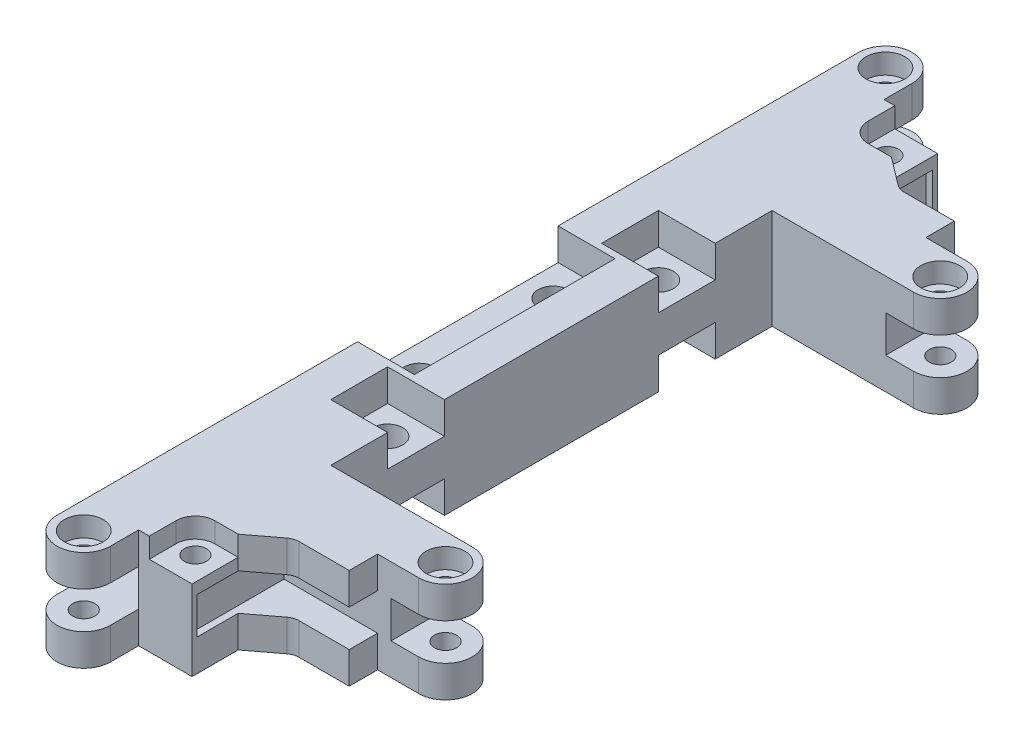
SolidWorks part; units mm, degrees
ref_plane "Front Plane" through (0, 0, 0) normal (0, 0, 1) x (1, 0, 0)
ref_plane "Top Plane" through (0, 0, 0) normal (0, 1, 0) x (1, 0, 0)
ref_plane "Right Plane" through (0, 0, 0) normal (1, 0, 0) x (0, 0, -1)
sketch "Sketch1" plane through (0, 0, 0) normal (0, 1, 0) x (1, 0, 0)
  line L0 (0, 0) -> (0, 41)
  line L1 (0, 41) -> (0, 45.25)
  line L2 (-7.5, 49.75) -> (0, 49.75)
  line L3 (0, 41) -> (6.15, 41)
  line L4 (0, 33) -> (6.15, 33)
  line L5 (0, 45.25) -> (-7.5, 45.25)
  line L6 (0, 49.75) -> (0, 55.75)
  line L7 (0, 55.75) -> (-21, 55.75)
  line L8 (-21, 55.75) -> (-21, 59.95)
  line L9 (-29, 25.8016) -> (-29, 59.95)
  line L10 (-29, 25.8016) -> (-29, 0)
  line L11 (-29, 0) -> (0, 0)
  line L12 (-29, 15) -> (-20.5, 15)
  line L13 (-20.5, 15) -> (-20.5, 0)
  line L14 (0, 33) -> (-15, 33)
  line L15 (-15, 33) -> (-15, 0)
  line L16 (0, 52.75) -> (-13, 52.75)
  line L17 (-13, 52.75) -> (-13, 43)
  line L18 (-13, 43) -> (0, 43)
  line L19 (-13, 52.75) -> (-13, 55.75)
  line L20 (-19.4, 51.75) -> (-19.4, 55.75)
  line L21 (-16.5, 48.85) -> (-13, 48.85)
  line L22 (-15, 16) -> (-23.5, 16)
  line L23 (-23.5, 16) -> (-23.5, 24.5)
  line L24 (-23.5, 24.5) -> (-15, 24.5)
  line L25 (-8.8604, 45.7078) -> (-13, 48.85)
  arc A0 (-7.5, 49.75) -> (-7.5, 45.25) centre (-7.5, 47.5) ccw
  arc A1 (6.15, 41) -> (6.15, 33) centre (6.15, 37) cw
  circle A2 centre (6.15, 37) radius 1.65
  arc A3 (-29, 59.95) -> (-21, 59.95) centre (-25, 59.95) cw
  circle A4 centre (-25, 59.95) radius 1.65
  circle A5 centre (-24.75, 10) radius 2.25
  circle A6 centre (-7.5, 47.5) radius 6.5 construction
  circle A7 centre (-16.5, 51.75) radius 1.65
  circle A8 centre (-25, 59.95) radius 2.9
  circle A9 centre (-16.5, 51.75) radius 2.9
  circle A10 centre (6.15, 37) radius 2.9
  circle A11 centre (-19.25, 20.25) radius 2.25
  point P26 (-24.75, 15)
  point P48 (-23.5, 20.25)
  point P53 (-19.25, 24.5)
  dimension "D1" = 6.15
  dimension "D2" = 3.3
  dimension "D4" = 8
  dimension "D5" = 3.3
  dimension "D15" = 10
  dimension "D16" = 4.5
  dimension "D17" = 13
  dimension "D21" = 3.5
  dimension "D23" = 5.8
  dimension "D24" = 8.5
  dimension "D3" = 8
  dimension "D6" = 6
  dimension "D7" = 4.5
  dimension "D8" = 6.5
  dimension "D9" = 7.5
  dimension "D10" = 4.2
  dimension "D11" = 25
  dimension "D12" = 15
  dimension "8" = 33
  dimension "D13" = 15
  dimension "D14" = 8.5
  dimension "D18" = 3
  dimension "D19" = 2
  dimension "D20" = 13
  dimension "D22" = 4
  dimension "D25" = 1
  dimension "D26" = 8.5
extrude "Boss-Extrude1" add sketch "Sketch1" along normal blind 7.5 and the other way blind 7.5 contours A3 L9 L10 L12 L13 L11 L0 L1 L5 A0 L2 L6 L7 L8 A4 | L13 L12 L10 L11 A5 | A1 L3 L0 L4 A2 | A5 | A8 A4 | A9 A7 | A10 A2 | A9 L17 L19 L7 L20 | L24 L23 L22 L15 A11 | A0 L25 L17 L18 L1 L5 region at (-19.0736, 0, -34.823) region at (0.1292, 0, -37) region at (-24.75, 0, -7.1437) region at (-19.25, 0, -16.1202) region at (-7.6123, 0, -44.6514) region at (-14.75, 0, -48.9441) region at (-18.4926, 0, -49.7574) region at (-24.75, 0, -10) region at (-27.818, 0, -59.95) region at (3.332, 0, -37)
sketch "Sketch2" plane through (0, 0, 0) normal (1, 0, 0) x (0, 0, -1)
  line L0 (55.75, -7.5) -> (55.75, 7.5) construction
  line L1 (55.75, 2.75) -> (63.95, 2.75)
  line L2 (55.75, 2.75) -> (55.75, -2.75)
  line L3 (55.75, -2.75) -> (63.95, -2.75)
  line L4 (63.95, 2.75) -> (63.95, -2.75)
  line L5 (55, 2.75) -> (41, 2.75)
  line L6 (55, 2.75) -> (55, -2.75)
  line L7 (55, -2.75) -> (41, -2.75)
  line L8 (41, 2.75) -> (41, -2.75)
  line L9 (41, -7.5) -> (41, 7.5) construction
  line L10 (63.95, -7.5) -> (63.95, 7.5) construction
  line L11 (55.75, 7.5) -> (48.85, 7.5) construction
  point P12 (63.95, 0)
  dimension "D1" = 14
  dimension "D2" = 5.5
extrude "Cut-Extrude1" cut sketch "Sketch2" against normal through all contours L1 L6 L3 L4 region at (0, 0, -59.85)
extrude "Cut-Extrude7" cut sketch "Sketch2<5>" against normal blind 14 contours L5 L8 L7 L6 region at (0, 0, -48)
sketch "Sketch2<5>" plane through (0, 0, 0) normal (1, 0, 0) x (0, 0, -1) same geometry as "Sketch2"
sketch "Sketch5" plane through (0, 0, 0) normal (1, 0, 0) x (0, 0, -1)
  line L0 (0, 0) -> (41, 0) construction
  line L1 (63.95, 2.75) -> (25.45, 2.75)
  line L2 (63.95, 2.75) -> (63.95, -2.75)
  line L3 (63.95, -2.75) -> (25.45, -2.75)
  line L4 (25.45, 2.75) -> (25.45, -2.75)
  line L5 (63.95, 2.75) -> (63.95, 7.5) construction
  point P4 (25.45, 0)
  dimension "D1" = 5.5
  dimension "D2" = 34.5
extrude "Cut-Extrude8" cut sketch "Sketch5" along normal blind 8 from surface starting at face at (-29, 0, -43.9125)
sketch "Sketch4" plane through (0, 0, 0) normal (1, 0, 0) x (0, 0, -1)
  line L1 (33, 2.75) -> (41, 2.75)
  line L2 (33, 2.75) -> (33, -2.75)
  line L3 (33, -2.75) -> (41, -2.75)
  line L4 (41, 2.75) -> (41, -2.75)
  line L6 (33, -7.5) -> (33, 7.5) construction
  point P4 (33, 0)
  dimension "D1" = 5.5
  dimension "D2" = 8
extrude "Cut-Extrude4" cut sketch "Sketch4" along normal through all from offset 2
extrude "Cut-Extrude5" cut sketch "Sketch1<3>" against normal through all from offset 2.75 contours L13 L12 L10 L11 A5 | A5 | L24 L23 L22 L15 A11 region at (-24.75, 0, -7.1437) region at (-19.25, 0, -16.1202) region at (-24.75, 0, -10) offset against normal yes
sketch "Sketch1<3>" plane through (0, 0, 0) normal (0, 1, 0) x (1, 0, 0) same geometry as "Sketch1"
mirror "Mirror2" about plane through (0, 0, 0) normal (0, 1, 0) of "Cut-Extrude5"
extrude "Cut-Extrude6" cut sketch "Sketch1<4>" against normal through all both and the other way through all contours A5 region at (-24.75, 0, -10)
sketch "Sketch1<4>" plane through (0, 0, 0) normal (0, 1, 0) x (1, 0, 0) same geometry as "Sketch1"
extrude "Cut-Extrude9" cut sketch "Sketch1<5>" against normal blind 3 from surface contours A8 A4 | A9 A7 | A10 A2 | A9 L17 L19 L7 L20 region at (-14.75, 0, -48.9441) region at (-18.4926, 0, -49.7574) region at (-27.818, 0, -59.95) region at (3.332, 0, -37) starting at face at (-13.7049, 7.5, -33.9673)
sketch "Sketch1<5>" plane through (0, 0, 0) normal (0, 1, 0) x (1, 0, 0) same geometry as "Sketch1"
sketch "Sketch6" plane through (0, 0, 0) normal (0, 1, 0) x (1, 0, 0)
  line L1 (-21.6514, 59.95) -> (-23.3257, 62.85)
  line L2 (-23.3257, 62.85) -> (-26.6743, 62.85)
  line L3 (-26.6743, 62.85) -> (-28.3486, 59.95)
  line L4 (-28.3486, 59.95) -> (-26.6743, 57.05)
  line L5 (-26.6743, 57.05) -> (-23.3257, 57.05)
  line L6 (-23.3257, 57.05) -> (-21.6514, 59.95)
  line L7 (-13.1514, 51.75) -> (-14.8257, 54.65)
  line L8 (-14.8257, 54.65) -> (-18.1743, 54.65)
  line L9 (-18.1743, 54.65) -> (-19.8486, 51.75)
  line L10 (-19.8486, 51.75) -> (-18.1743, 48.85)
  line L11 (-18.1743, 48.85) -> (-14.8257, 48.85)
  line L12 (-14.8257, 48.85) -> (-13.1514, 51.75)
  line L13 (9.4986, 37) -> (7.8243, 39.9)
  line L14 (7.8243, 39.9) -> (4.4757, 39.9)
  line L15 (4.4757, 39.9) -> (2.8014, 37)
  line L16 (2.8014, 37) -> (4.4757, 34.1)
  line L17 (4.4757, 34.1) -> (7.8243, 34.1)
  line L18 (7.8243, 34.1) -> (9.4986, 37)
  circle A0 centre (-25, 59.95) radius 2.9 construction
  circle A1 centre (-16.5, 51.75) radius 2.9 construction
  circle A2 centre (6.15, 37) radius 2.9 construction
  dimension "D1" = 5.8
extrude "Cut-Extrude10" cut sketch "Sketch6" along normal blind 2.2 from surface starting at face at (-25, -7.5, -58.3)
mirror "Mirror3" about plane through (0, 0, 0) normal (0, 0, 1) of bodies 112 107
